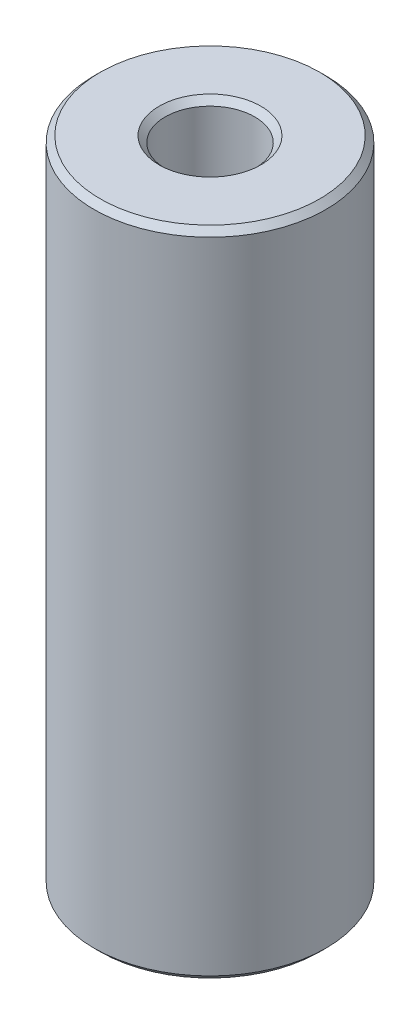
SolidWorks part; units mm, degrees
ref_plane "Front Plane" through (0, 0, 0) normal (0, 0, 1) x (1, 0, 0)
ref_plane "Top Plane" through (0, 0, 0) normal (0, 1, 0) x (1, 0, 0)
ref_plane "Right Plane" through (0, 0, 0) normal (1, 0, 0) x (0, 0, -1)
sketch "Sketch1" plane through (0, 0, 0) normal (0, 1, 0) x (1, 0, 0)
  circle A0 centre (0, 0) radius 55
  dimension "SLEEVE_OD" = 110
extrude "Boss-Extrude1" add sketch "Sketch1" along normal blind 309.4181
sketch "Sketch2" plane through (0, 0, 0) normal (0, 1, 0) x (1, 0, 0)
  circle A0 centre (0, 0) radius 21.236
  dimension "BORE_D" = 42.4721
extrude "Cut-Extrude1" cut sketch "Sketch2" along normal through all
chamfer "Chamfer1" distance 2.9196 angle 45 4 edges at (0, 309.4181, 21.236) (0, 0, 21.236) (0, 0, 55) (0, 309.4181, 55)
